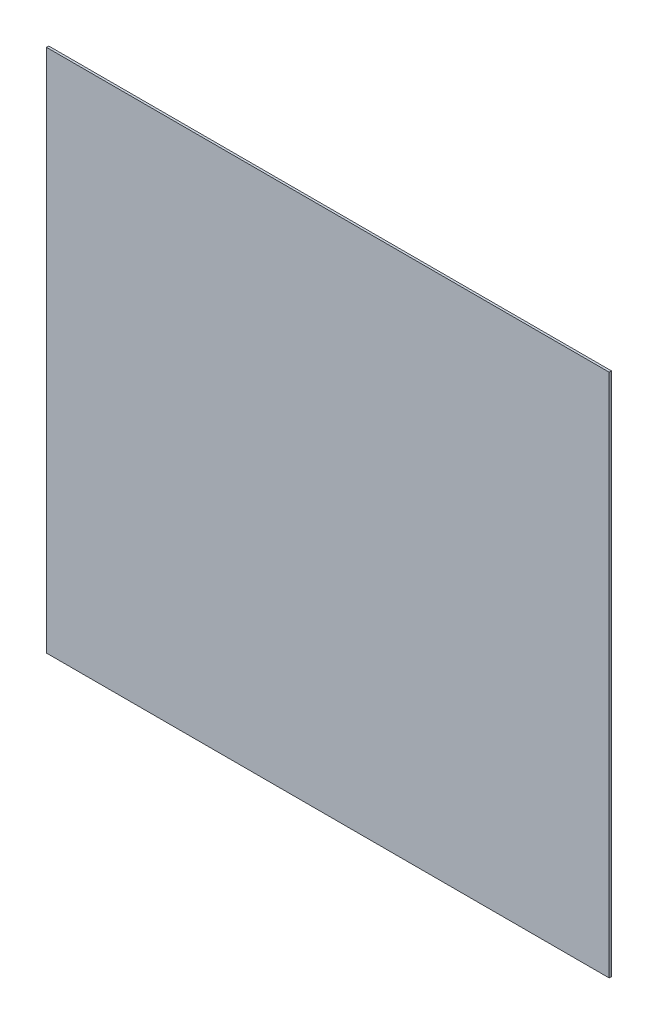
SolidWorks part; units mm, degrees
material "Mahogany"
ref_plane "Front Plane" through (0, 0, 0) normal (0, 0, 1) x (1, 0, 0)
ref_plane "Top Plane" through (0, 0, 0) normal (0, 1, 0) x (1, 0, 0)
ref_plane "Right Plane" through (0, 0, 0) normal (1, 0, 0) x (0, 0, -1)
sketch "Sketch1" plane through (0, 0, 0) normal (0, 0, 1) x (1, 0, 0)
  line L1 (-391.5, -365) -> (391.5, -365)
  line L2 (-391.5, -365) -> (-391.5, 365)
  line L3 (-391.5, 365) -> (391.5, 365)
  line L4 (391.5, -365) -> (391.5, 365)
  line L5 (-391.5, -365) -> (391.5, 365) construction
  line L6 (-391.5, 365) -> (391.5, -365) construction
  point P0 (0, 0)
  dimension "D1" = 783
  dimension "D2" = 730
extrude "Boss-Extrude1" add sketch "Sketch1" along normal blind 3.175
equation "\"W\"= 1700"
equation "\"L\"= 760"
equation "\"H\"= 810"
equation "\"ARM_BOLT_SPACING\"= 140"
equation "\"ARM_TO_WALL\"= 300"
equation "\"D1@Sketch1\"=(\"W\"/2)-(52 + 15)"
equation "\"D2@Sketch1\"=\"H\"-(65+15)"
